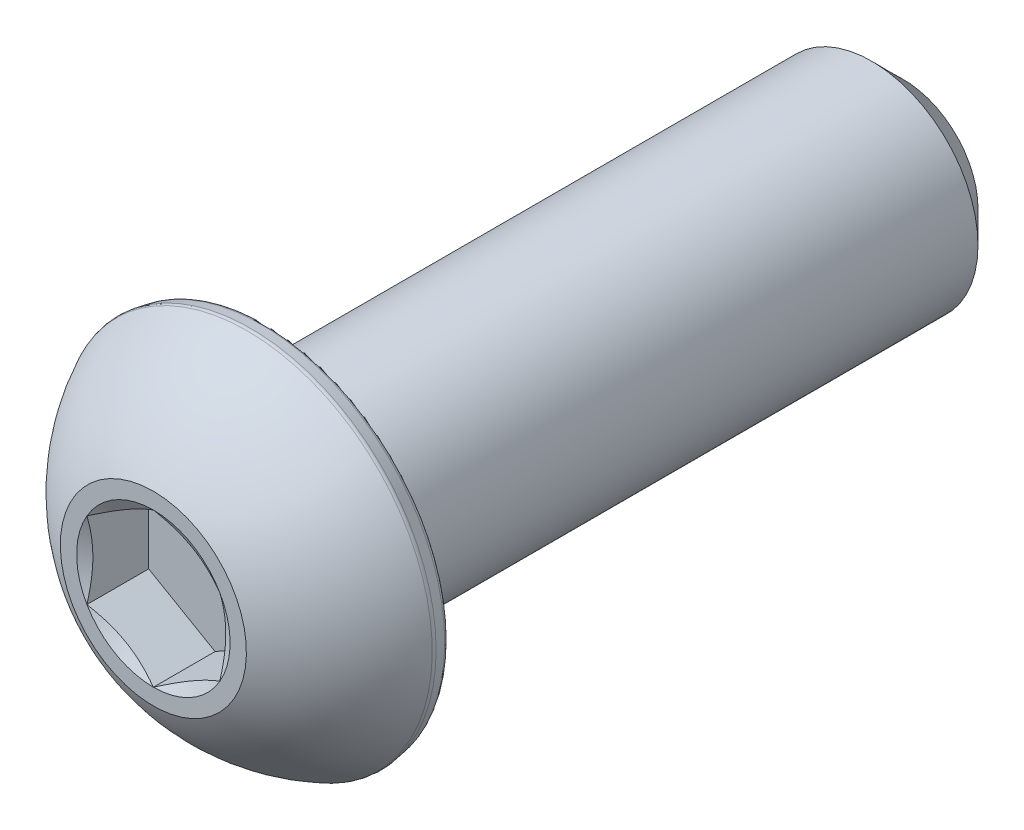
SolidWorks part; units mm, degrees
ref_plane "Front Plane" through (0, 0, 0) normal (0, 0, 1) x (1, 0, 0)
ref_plane "Top Plane" through (0, 0, 0) normal (0, 1, 0) x (1, 0, 0)
ref_plane "Right Plane" through (0, 0, 0) normal (1, 0, 0) x (0, 0, -1)
sketch "Sketch1" plane through (0, 0, 0) normal (1, 0, 0) x (0, 0, -1)
  line L0 (-11.2014, 0) -> (11.2014, 0) construction
  line L1 (-11.2014, 0) -> (-11.2014, 5.5499)
  line L2 (-11.2014, 5.5499) -> (-7.8486, 5.5499)
  line L3 (-7.8486, 5.5499) -> (-7.8486, 3.175)
  line L4 (-7.8486, 3.175) -> (11.2014, 3.175)
  line L5 (11.2014, 3.175) -> (11.2014, 0)
  point P2 (0, 0)
  point P4 (9.9314, 0)
  point P9 (9.2964, 3.175)
  point P10 (9.2964, -3.175)
  point P11 (11.2014, -3.175)
  point P15 (-9.3574, 0)
  dimension "Head Height" = 3.3528
  dimension "Head Diameter" = 11.0998
  dimension "Length" = 19.05
  dimension "Screw Size Decimal Equivalent" = 6.35
  dimension "Thread Pitch" = 1.27
  dimension "D1" = 1.905
  dimension "D2" = 1.844
sketch "Sketch2" plane through (0, 0, 0) normal (0, 0, 1) x (1, 0, 0)
  line L0 (0, 3.175) -> (0, 0) construction
  line L1 (0, 2.2914) -> (-1.9844, 1.1457)
  line L2 (-1.9844, 1.1457) -> (-1.9844, -1.1457)
  line L3 (-1.9844, -1.1457) -> (0, -2.2914)
  line L4 (0, -2.2914) -> (1.9844, -1.1457)
  line L5 (1.9844, -1.1457) -> (1.9844, 1.1457)
  line L6 (1.9844, 1.1457) -> (0, 2.2914)
  circle A0 centre (0, 0) radius 1.9844 construction
  circle A1 centre (0, 0) radius 2.7781
  point P10 (0, 2.7781)
  dimension "D1" = 5.5563
  dimension "Drive Size" = 3.9688
sketch "Sketch3" plane through (0, 0, 0) normal (1, 0, 0) x (0, 0, -1)
  line L0 (-11.2014, 0) -> (-11.2014, 2.7781)
  line L1 (-11.2014, 0) -> (-11.2014, 5.5499) construction
  line L2 (-11.2014, 5.5499) -> (-7.8486, 5.5499) construction
  line L3 (-8.3515, 5.5499) -> (-7.8486, 5.4612)
  line L4 (-7.8486, 5.5499) -> (-7.8486, 3.175) construction
  line L5 (-7.8486, 5.4612) -> (-7.8486, 3.175)
  line L6 (-11.2014, 0) -> (11.2014, 0) construction
  line L7 (-11.2014, 0) -> (11.2014, 0)
  line L8 (11.2014, 0) -> (11.2014, 2.2225)
  line L9 (11.2014, 3.175) -> (11.2014, 0) construction
  line L10 (11.2014, 2.2225) -> (10.2489, 3.175)
  line L11 (-7.8486, 3.175) -> (11.2014, 3.175) construction
  line L12 (10.2489, 3.175) -> (-7.8486, 3.175)
  arc A0 (-11.2014, 2.7781) -> (-8.3515, 5.5499) centre (-5.7266, 0) cw
  dimension "D1" = 0.5029
  dimension "D2" = 10
  dimension "D3" = 45
  dimension "D4" = 0.9525
revolve "Revolve1" add sketch "Sketch3" angle 360 about L7
sketch "Sketch4" plane through (0, 0, 11.2014) normal (0, 0, 1) x (1, 0, 0)
  line L0 (-1.9844, -1.1457) -> (0, -2.2914) construction
  line L1 (-1.9844, 1.1457) -> (-1.9844, -1.1457) construction
  line L2 (0, 2.2914) -> (-1.9844, 1.1457) construction
  line L3 (1.9844, 1.1457) -> (0, 2.2914) construction
  line L4 (1.9844, -1.1457) -> (1.9844, 1.1457) construction
  line L5 (0, -2.2914) -> (1.9844, -1.1457) construction
  line L6 (-1.9844, -1.1457) -> (0, -2.2914)
  line L7 (-1.9844, 1.1457) -> (-1.9844, -1.1457)
  line L8 (0, 2.2914) -> (-1.9844, 1.1457)
  line L9 (1.9844, 1.1457) -> (0, 2.2914)
  line L10 (1.9844, -1.1457) -> (1.9844, 1.1457)
  line L11 (0, -2.2914) -> (1.9844, -1.1457)
extrude "Cut-Extrude1" cut sketch "Sketch4" against normal up to vertex (1.844 mm away) up to point (0, 0, 9.3574)
sketch "Sketch5" plane through (0, 0, 11.2014) normal (0, 0, 1) x (1, 0, 0)
  circle A0 centre (0, 0) radius 2.2914
extrude "Cut-Extrude2" cut sketch "Sketch5" against normal up to vertex (1.844 mm away) draft 60 up to point (0, 0, 9.3574)
fillet "Fillet1" radius 0.1676 2 edges at (5.5499, 0, 8.3515) (5.4612, 0, 7.8486)
split "Split1" [suppressed] bodies to split 106
sketch "Sketch6" [suppressed] plane through (0, 0, -11.2014) normal (0, 0, -1) x (-1, 0, 0)
  circle A0 centre (0, 0) radius 3.175 construction
  circle A1 centre (0, 0) radius 3.175
curve "Helix/Spiral1" [suppressed] pitch 1.27 height 20.32 turns 16
sketch "Sketch7" [suppressed] plane through (0, 0, 0) normal (1, 0, 0) x (0, 0, -1)
  line L0 (11.122, 3.3125) -> (11.757, 2.2126) construction
  line L1 (11.757, 2.2126) -> (12.392, 3.3125) construction
  line L2 (12.392, 3.3125) -> (11.122, 3.3125) construction
  line L3 (11.1617, 3.2437) -> (12.3523, 3.2437)
  line L4 (12.3523, 3.2437) -> (11.8364, 2.3501)
  line L5 (11.8364, 2.3501) -> (11.6777, 2.3501)
  line L6 (11.6777, 2.3501) -> (11.1617, 3.2437)
  line L7 (11.757, 2.3501) -> (11.757, 2.2126) construction
  line L8 (11.2014, 3.175) -> (12.3127, 3.175) construction
  line L9 (11.757, 3.3125) -> (11.757, 3.175) construction
  point P12 (11.757, 3.2437)
  dimension "D1" = 1.27
  dimension "D2" = 0.1588
sweep "Cut-Sweep1" [suppressed] cut profiles "Sketch7" path "Helix/Spiral1"
sketch "Sketch8" [suppressed] plane through (0, 0, 7.8486) normal (0, 0, -1) x (-1, 0, 0)
  circle A0 centre (0, 0) radius 3.3125
extrude "Boss-Extrude1" [suppressed] add sketch "Sketch8" along normal up to vertex draft 45 up to point (0, 3.175, -9.2964)
equation "\"D1@Sketch1\"=\"Thread Pitch@Sketch1\"*1.5"
equation "\"D2@Sketch1\"=0.55*\"Head Height@Sketch1\""
equation "\"D1@Sketch2\"=\"Drive Size@Sketch2\"*1.4"
equation "\"D1@Sketch3\"=0.15*\"Head Height@Sketch1\""
equation "\"D4@Sketch3\"=0.75*\"Thread Pitch@Sketch1\""
equation "\"D1@Fillet1\"=.05*\"Head Height@Sketch1\""
equation "\"D4@Helix/Spiral1\"=\"Thread Pitch@Sketch1\""
equation "\"D3@Helix/Spiral1\"=\"Length@Sketch1\"+\"Thread Pitch@Sketch1\""
equation "\"D2@Sketch7\"=\"D1@Sketch7\"/8"
equation "\"D1@Sketch7\"=\"Thread Pitch@Sketch1\""
